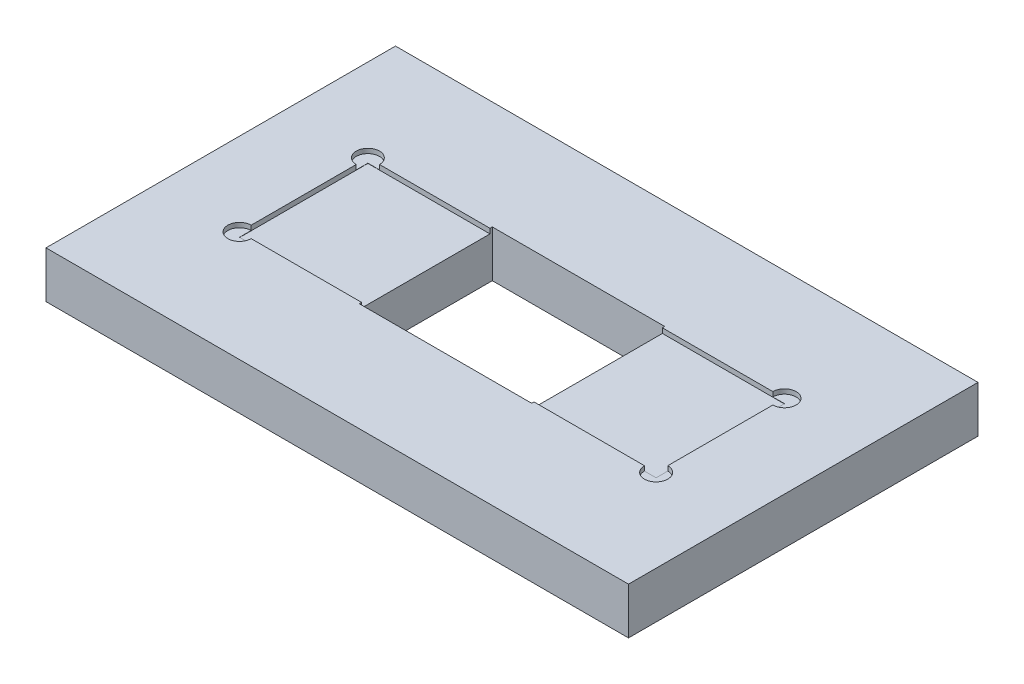
SolidWorks part; units mm, degrees
material "Plain Carbon Steel"
ref_plane "Front Plane" through (0, 0, 0) normal (0, 0, 1) x (1, 0, 0)
ref_plane "Top Plane" through (0, 0, 0) normal (0, 1, 0) x (1, 0, 0)
ref_plane "Right Plane" through (0, 0, 0) normal (1, 0, 0) x (0, 0, -1)
sketch "Sketch1" plane through (0, 0, 0) normal (0, 1, 0) x (1, 0, 0)
  line L1 (-125, -75) -> (125, -75)
  line L2 (-125, -75) -> (-125, 75)
  line L3 (-125, 75) -> (125, 75)
  line L4 (125, -75) -> (125, 75)
  line L5 (-125, -75) -> (125, 75) construction
  line L6 (-125, 75) -> (125, -75) construction
  point P0 (0, 0)
  dimension "D1" = 250
  dimension "D2" = 150
extrude "Boss-Extrude1" add sketch "Sketch1" against normal blind 20
sketch "Sketch2" plane through (0, 0, 0) normal (0, 1, 0) x (1, 0, 0)
  line L1 (-89.4, -27.55) -> (89.4, -27.55)
  line L2 (-89.4, -27.55) -> (-89.4, 27.55)
  line L3 (-89.4, 27.55) -> (89.4, 27.55)
  line L4 (89.4, -27.55) -> (89.4, 27.55)
  line L5 (-89.4, -27.55) -> (89.4, 27.55) construction
  line L6 (-89.4, 27.55) -> (89.4, -27.55) construction
  point P0 (0, 0)
  dimension "D1" = 178.8
  dimension "D2" = 55.1
extrude "Cut-Extrude1" cut sketch "Sketch2" against normal blind 2.1
sketch "Sketch3" plane through (0, 0, 0) normal (0, 1, 0) x (1, 0, 0)
  circle A0 centre (-89.4, 27.55) radius 5
  circle A1 centre (89.4, 27.55) radius 5
  circle A2 centre (89.4, -27.55) radius 5
  circle A3 centre (-89.4, -27.55) radius 5
  dimension "D1" = 10
extrude "Cut-Extrude2" cut sketch "Sketch3" against normal blind 2
sketch "Sketch4" plane through (0, -2.1, 0) normal (0, 1, 0) x (1, 0, 0)
  line L1 (-37, -28.55) -> (37, -28.55)
  line L2 (-37, -28.55) -> (-37, 28.55)
  line L3 (-37, 28.55) -> (37, 28.55)
  line L4 (37, -28.55) -> (37, 28.55)
  line L6 (89.4, 27.55) -> (-89.4, 27.55) construction
  line L7 (-84.4, -27.55) -> (84.4, -27.55) construction
  point P8 (0, -28.55)
  dimension "D1" = 74
  dimension "D2" = 1
  dimension "D3" = 1
extrude "Cut-Extrude3" cut sketch "Sketch4" against normal through all both and the other way through all
